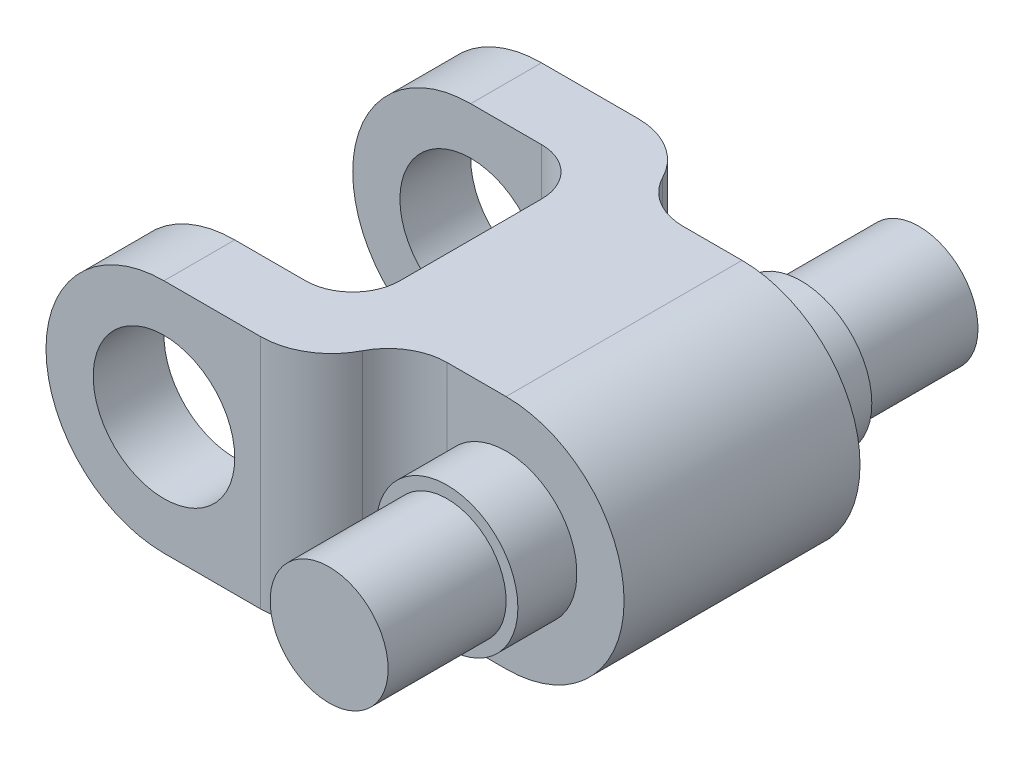
SolidWorks part; units mm, degrees
material "1060 Alloy"
ref_plane "Front Plane" through (0, 0, 0) normal (0, 0, 1) x (1, 0, 0)
ref_plane "Top Plane" through (0, 0, 0) normal (0, 1, 0) x (1, 0, 0)
ref_plane "Right Plane" through (0, 0, 0) normal (1, 0, 0) x (0, 0, -1)
sketch "Sketch1" plane through (0, 0, 0) normal (0, 0, 1) x (1, 0, 0)
  line L0 (0, 5) -> (-5, 5)
  line L1 (-5, 5) -> (-5, -5)
  line L2 (-5, -5) -> (0, -5)
  arc A0 (0, 5) -> (0, -5) centre (0, 0) cw
  circle A1 centre (0, 0) radius 2.5
  circle A2 centre (0, 0) radius 3
  dimension "D1" = 5
  dimension "D3" = 5
  dimension "D4" = 6
  dimension "D2" = 5
extrude "Boss-Extrude1" add sketch "Sketch1" along normal mid plane 10 contours A0 L0 L1 L2 A2 region at (4.8586, 0, 0)
extrude "Boss-Extrude2" add sketch "Sketch1<3>" along normal mid plane 15 contours A2
sketch "Sketch1<3>" plane through (0, 0, 0) normal (0, 0, 1) x (1, 0, 0) same geometry as "Sketch1"
extrude "Boss-Extrude3" add sketch "Sketch1<4>" along normal mid plane 25 contours A1
sketch "Sketch1<4>" plane through (0, 0, 0) normal (0, 0, 1) x (1, 0, 0) same geometry as "Sketch1"
sketch "Sketch5" plane through (0, 0, 0) normal (0, 0, 1) x (1, 0, 0)
  line L0 (-5, 5) -> (-5, -5)
  line L1 (-5, 5) -> (-11.5, 5)
  line L3 (-11.5, -5) -> (-5, -5)
  arc A0 (-11.5, 5) -> (-11.5, -5) centre (-11.5, 0) ccw
  dimension "D1" = 6.5
extrude "Boss-Extrude4" add sketch "Sketch5" along normal mid plane 16
sketch "Sketch6" plane through (0, 5, 0) normal (0, 1, 0) x (1, 0, 0)
  line L0 (-16.5, 8) -> (-16.5, -8) construction
  line L1 (-6.5, 5) -> (-16.5, 5)
  line L2 (-6.5, 5) -> (-6.5, -5)
  line L3 (-6.5, -5) -> (-16.5, -5)
  line L4 (-16.5, 5) -> (-16.5, -5)
  line L8 (0, -5) -> (-5, -5) construction
  line L9 (0, 5) -> (-5, 5) construction
  dimension "D1" = 10
extrude "Cut-Extrude1" cut sketch "Sketch6" against normal through all both and the other way through all contours L4 L3 L2 L1
sketch "Sketch7" plane through (0, 0, -8) normal (0, 0, -1) x (-1, 0, 0)
  circle A0 centre (11.5, 0) radius 3
  dimension "D1" = 6
extrude "Cut-Extrude2" cut sketch "Sketch7" against normal through all
fillet "Fillet4" radius 2.5 2 edges at (-5, 0, 5) (-5, 0, -5)
fillet "Fillet5" radius 3 2 edges at (-5, 0, -8) (-5, 0, 8)
fillet "Fillet6" radius 2 2 edges at (-6.5, 0, 5) (-6.5, 0, -5)
